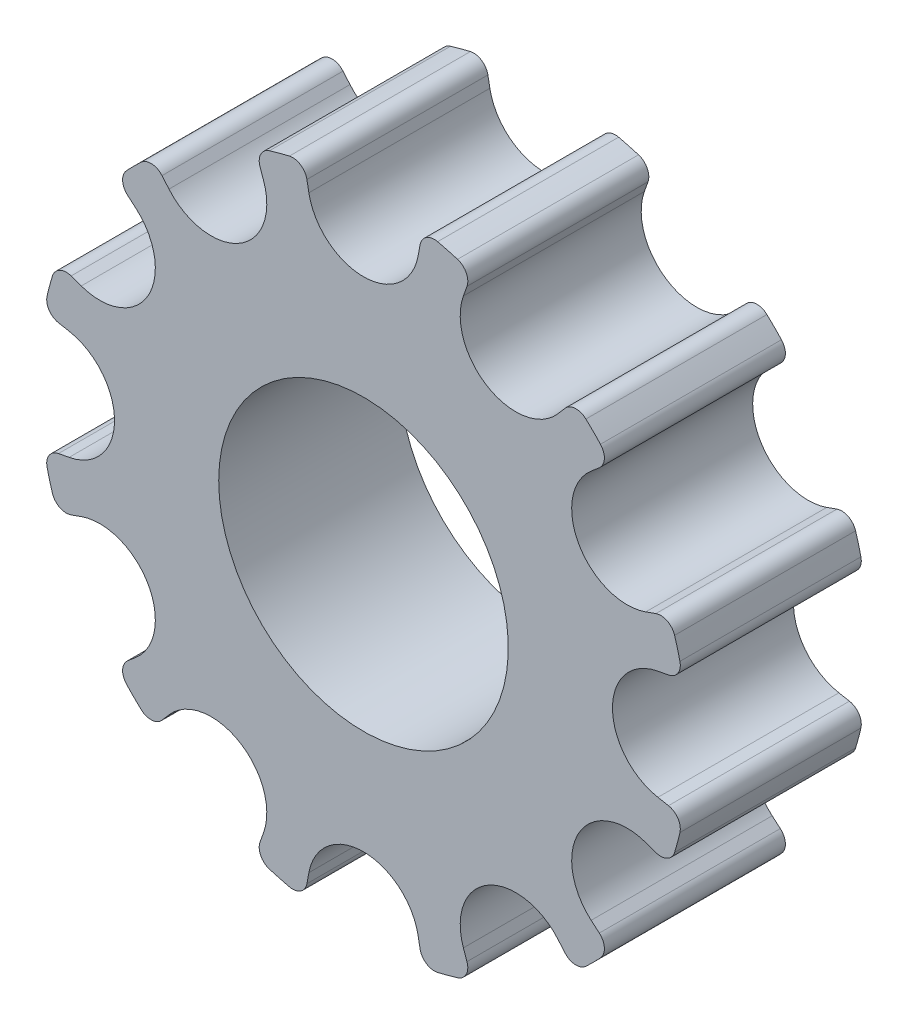
SolidWorks part; units mm, degrees
ref_plane "정면" through (0, 0, 0) normal (0, 0, 1) x (1, 0, 0)
ref_plane "윗면" through (0, 0, 0) normal (0, 1, 0) x (1, 0, 0)
ref_plane "우측면" through (0, 0, 0) normal (1, 0, 0) x (0, 0, -1)
sketch "스케치3" plane through (0, 0, 0) normal (0, 0, 1) x (1, 0, 0)
  line L0 (0, 0) -> (0, 8.9778) construction
  line L1 (0, 0) -> (-4.7746, 8.2699) construction
  line L2 (0, 8.9778) -> (0, 10.6778) construction
  line L3 (-1.5092, 8.1327) -> (-1.6381, 8.8271)
  line L4 (1.5092, 8.1327) -> (1.6381, 8.8271)
  circle A0 centre (0, 0) radius 9.5493 construction
  circle A1 centre (0, 0) radius 10.6778 construction
  circle A2 centre (0, 0) radius 8.9778
  circle A3 centre (0, 8.4128) radius 1.535
  dimension "Pitch" = 19.0986
  dimension "D5" = 3.07
  dimension "Body" = 17.9556
  dimension "Degree" = 30
  dimension "D4" = 2.1
  dimension "Belt_Outside" = 3.8
extrude "보스-돌출2" add sketch "스케치3" along normal mid plane 5 contours A2
extrude "컷-돌출2" cut sketch "스케치3<3>" against normal through all both and the other way through all contours A3 A2 L3 | A2 A3 | A3 L4 A2 region at (0, 8.0345, 0) region at (-1.5561, 8.6644, 0) region at (1.5561, 8.6644, 0)
sketch "스케치3<3>" plane through (0, 0, 0) normal (0, 0, 1) x (1, 0, 0) same geometry as "스케치3"
fillet "필렛1" radius 0.4 2 edges at (1.6381, 8.8271, 0) (-1.6381, 8.8271, 0)
pattern_circular "원형 패턴1" count 12 over 360 about axis through (0, 0, 2.5) along (0, 0, -1) of "컷-돌출2", "필렛1"
sketch "스케치4" plane through (0, 0, -2.5) normal (0, 0, -1) x (-1, 0, 0)
  circle A0 centre (0, 0) radius 4
  dimension "D1" = 8
extrude "컷-돌출3" cut sketch "스케치4" against normal through all
equation "\"n\"= 12'number of teeth"
equation "\"Pitch@스케치3\" = 5 * \"n\" /  ( PI ) "
equation "\"Degree@스케치3\" = 360 / \"n\""
equation "\"D1@원형 패턴1\"=\"n\""
equation "\"Body@스케치3\" = \"Pitch@스케치3\" - 2 * 0.225 * 2.54"
